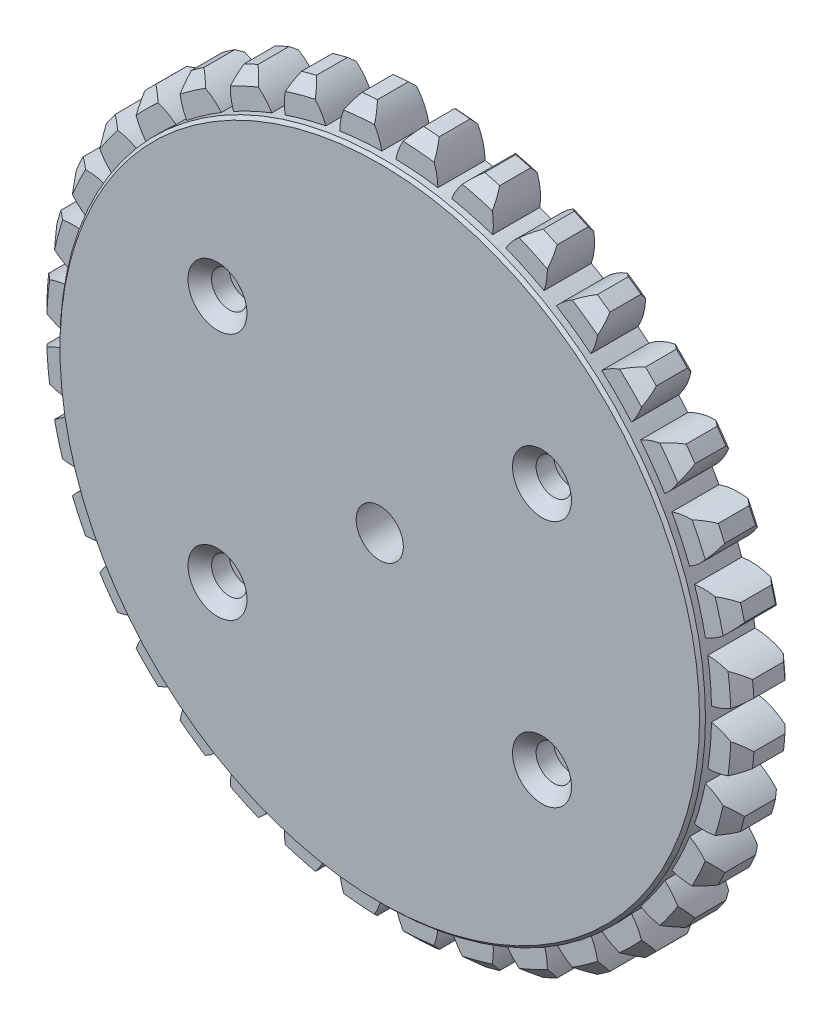
SolidWorks part; units mm, degrees
extrude "Gear Blank" add sketch "Sketch1" along normal mid plane 8
sketch "Sketch1" plane through (0, 0, 0) normal (0, 0, 1) x (1, 0, 0)
  circle A0 centre (0, 0) radius 60
  dimension "D1" = 120
chamfer "Front Gear Chamfer" distance 2 angle 45 1 edges at (60, 0, 4)
ref_plane "Plane1" through (0, 0, 0) normal (0, 0, 1) x (1, 0, 0)
ref_plane "Plane2" through (0, 0, 0) normal (0, 1, 0) x (-1, 0, 0)
ref_plane "Plane3" through (0, 0, 0) normal (1, 0, 0) x (0, 0, -1)
chamfer "Rear Gear Chamfer" distance 0.75 angle 45 1 edges at (60, 0, -4)
sketch "Sketch2" plane through (0, 0, 0) normal (0, 0, 1) x (1, 0, 0)
  line L0 (0, 60) -> (0, 0) construction
  line L1 (0, 0) -> (9.6524, 0) construction
  line L2 (0, 0) -> (-3.9242, 59.8715) construction
  line L3 (0, 0) -> (3.9242, 59.8715) construction
  line L4 (0, 0) -> (1.1932, 54.687) construction
  line L5 (0, 0) -> (-1.1933, 54.687) construction
  arc A1 (3.9242, 59.8715) -> (-3.9242, 59.8715) centre (0, 0) ccw
  arc A2 (3.9242, 59.8715) -> (1.1932, 54.687) centre (11.0181, 52.8234) ccw
  arc A3 (-3.9242, 59.8715) -> (-1.1933, 54.687) centre (-11.0181, 52.8234) cw
  arc A4 (-1.1933, 54.687) -> (1.1932, 54.687) centre (0, 0) cw
  circle A5 centre (0, 0) radius 60 construction
  dimension "D2" = 10
  dimension "D1" = 109.4
extrude "Tooth Cut" cut sketch "Sketch2" against normal mid plane 8
pattern_circular "Tooth Copies" count 36 every 10 of "Tooth Cut"
sketch "Sketch3" plane through (0, 0, 4) normal (0, 0, 1) x (1, 0, 0)
  circle A0 centre (0, 0) radius 54.7
  arc A1 (-54.0634, -8.3212) -> (-53.6489, -10.6715) centre (0, 0) ccw construction
extrude "Boss-Extrude1" add sketch "Sketch3" along normal blind 1.54
chamfer "Chamfer1" distance 0.5 angle 45 1 edges at (54.7, 0, 5.54)
sketch "Sketch4" plane through (0, 0, -4) normal (0, 0, -1) x (-1, 0, 0)
  line L0 (30, 25) -> (25, 25) construction
  line L5 (-30, 25) -> (-30, -25) construction
  line L6 (-30, -25) -> (-25, -25) construction
  line L7 (30, -25) -> (30, 25) construction
  line L8 (25, 25) -> (25, -25) construction
  line L9 (-25, 25) -> (-25, -25) construction
  line L10 (25, -25) -> (30, -25) construction
  line L11 (-25, 25) -> (-30, 25) construction
  line L12 (0, -54.2) -> (0, 54.2) construction
  circle A1 centre (0, 0) radius 4
  circle A2 centre (27.5, -21) radius 1.5
  circle A3 centre (27.5, 21) radius 1.5
  circle A4 centre (0, 0) radius 54.2 construction
  circle A5 centre (-27.5, 21) radius 1.5
  circle A6 centre (-27.5, -21) radius 1.5
  dimension "D1" = 60
  dimension "D4" = 30
  dimension "D7" = 4
  dimension "D8" = 4
  dimension "D2" = 50
  dimension "D3" = 25
  dimension "D5" = 5
  dimension "D6" = 5
extrude "Cut-Extrude1" cut sketch "Sketch4" against normal blind 10
sketch "Sketch5" plane through (0, 0, 5.54) normal (0, 0, 1) x (1, 0, 0)
  circle A0 centre (-27.5, 21) radius 3
  circle A1 centre (27.5, -21) radius 3
  circle A2 centre (-27.5, -21) radius 3
  circle A3 centre (27.5, 21) radius 3
  point P8 (0, 0)
  dimension "D1" = 2
extrude "Cut-Extrude2" cut sketch "Sketch5" against normal blind 5
chamfer "Chamfer2" distance 2 angle 45 4 edges at (30.5, -21, 5.54) (-24.5, -21, 5.54) (-24.5, 21, 5.54) (30.5, 21, 5.54)
equation "\"D2@Tooth Copies\"=360/\"D1@Tooth Copies\""
equation "\"D4@Sketch2\" = (3/4) * \"D2@Tooth Copies\""
equation "\"D5@Sketch2\"= \"D2@Tooth Copies\" - \"D4@Sketch2\""
equation "\"D1@Sketch2\" = \"D1@Sketch1\" - 10.6"
equation "\"D1@Tooth Cut\" = \"D1@Gear Blank\""
